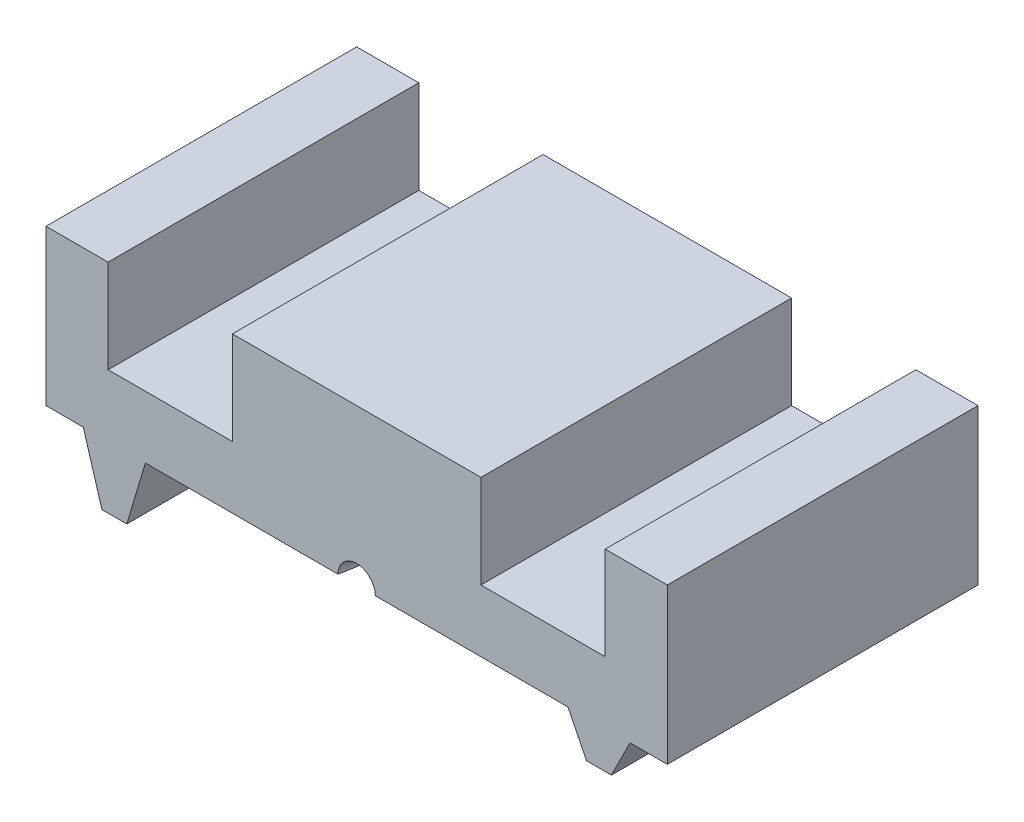
SolidWorks part; units mm, degrees
ref_plane "Plan de face" through (0, 0, 0) normal (0, 0, 1) x (1, 0, 0)
ref_plane "Plan de dessus" through (0, 0, 0) normal (0, 1, 0) x (1, 0, 0)
ref_plane "Plan de droite" through (0, 0, 0) normal (1, 0, 0) x (0, 0, -1)
sketch "Esquisse1" plane through (0, 0, 0) normal (0, 1, 0) x (1, 0, 0)
  line L1 (25, -12.5) -> (-25, -12.5)
  line L2 (25, -12.5) -> (25, 12.5)
  line L3 (25, 12.5) -> (-25, 12.5)
  line L4 (-25, -12.5) -> (-25, 12.5)
  dimension "D1" = 25
  dimension "D2" = 12.5
  dimension "D3" = 50
  dimension "D4" = 25
extrude "Boss.-Extru.1" add sketch "Esquisse1" against normal blind 12.5
sketch "Esquisse6" plane through (0, 0, 0) normal (0, 0, 1) x (1, 0, 0)
  line L0 (0, -20) -> (0, -5)
  line L2 (25, -12.5) -> (-25, -12.5) construction
  arc A0 (0, -20) -> (0, -5) centre (0, -12.5) cw
  dimension "D1" = 7.5
ref_axis "Axe1" [suppressed] through (0, -20, 0) along (0, 1, 0)
revolve "Enlèvement de matière-Révolution1" cut sketch "Esquisse6" angle 360 about L0
sketch "Esquisse8" plane through (0, 0, 0) normal (0, 0, 1) x (1, 0, 0)
  line L0 (25, -12.5) -> (-25, -12.5) construction
  line L1 (8, -12.5) -> (10, -12.5)
  arc A0 (10, -12.5) -> (8, -12.5) centre (9, -12.5) ccw
  dimension "D1" = 1
  dimension "D2" = 9
revolve "Enlèvement de matière-Révolution2" cut sketch "Esquisse8" angle 360 about axis through (0, -20, 0) along (0, 1, 0)
sketch "Esquisse13" plane through (0, 0, -12.5) normal (0, 0, -1) x (-1, 0, 0)
  line L0 (20, 0) -> (20, -7.5)
  line L1 (-25, 0) -> (25, 0) construction
  line L2 (20, -7.5) -> (10, -7.5)
  line L3 (10, -7.5) -> (10, 0)
  line L4 (20, 0) -> (10, 0)
  line L5 (-10, 0) -> (-10, -7.5)
  line L6 (-10, -7.5) -> (-20, -7.5)
  line L7 (-20, -7.5) -> (-20, 0)
  line L8 (25, -12.5) -> (25, 0) construction
  line L9 (-25, -12.5) -> (25, -12.5) construction
  line L10 (-25, -12.5) -> (-25, 0) construction
  line L11 (-10, 0) -> (-20, 0)
  dimension "D1" = 5
  dimension "D2" = 5
  dimension "D3" = 5
  dimension "D4" = 5
extrude "Enlèv. mat.-Extru.5" cut sketch "Esquisse13" against normal through all
sketch "Esquisse14" plane through (0, 0, 12.5) normal (0, 0, 1) x (1, 0, 0)
  line L0 (-25, -12.5) -> (25, -12.5) construction
  circle A0 centre (0, -12.5) radius 1.5
  dimension "D1" = 3
extrude "Enlèv. mat.-Extru.6" cut sketch "Esquisse14" against normal blind 4 draft 10
sketch "Esquisse15" plane through (0, 0, -12.5) normal (0, 0, -1) x (-1, 0, 0)
  line L0 (-22, -12.5) -> (-20.5, -15.5)
  line L1 (-25, -12.5) -> (25, -12.5) construction
  line L2 (-20.5, -15.5) -> (-18.5, -15.5)
  line L3 (-18.5, -15.5) -> (-17, -12.5)
  line L4 (22, -12.5) -> (20.5, -17.5)
  line L5 (20.5, -17.5) -> (18.5, -17.5)
  line L6 (18.5, -17.5) -> (17, -12.5)
  line L7 (22, -12.5) -> (17, -12.5)
  line L8 (-17, -12.5) -> (-22, -12.5)
  dimension "D1" = 3
  dimension "D2" = 5
  dimension "D3" = 1.5
  dimension "D4" = 2
  dimension "D5" = 3
  dimension "D6" = 2
  dimension "D7" = 5
  dimension "D8" = 1.5
  dimension "D9" = 3
  dimension "D10" = 5
extrude "Boss.-Extru.2" add sketch "Esquisse15" against normal up to surface (25 mm away) contours L4 L5 L6 L7 | L0 L2 L3 L8 up to face at (0, -5.6071, 12.5)
